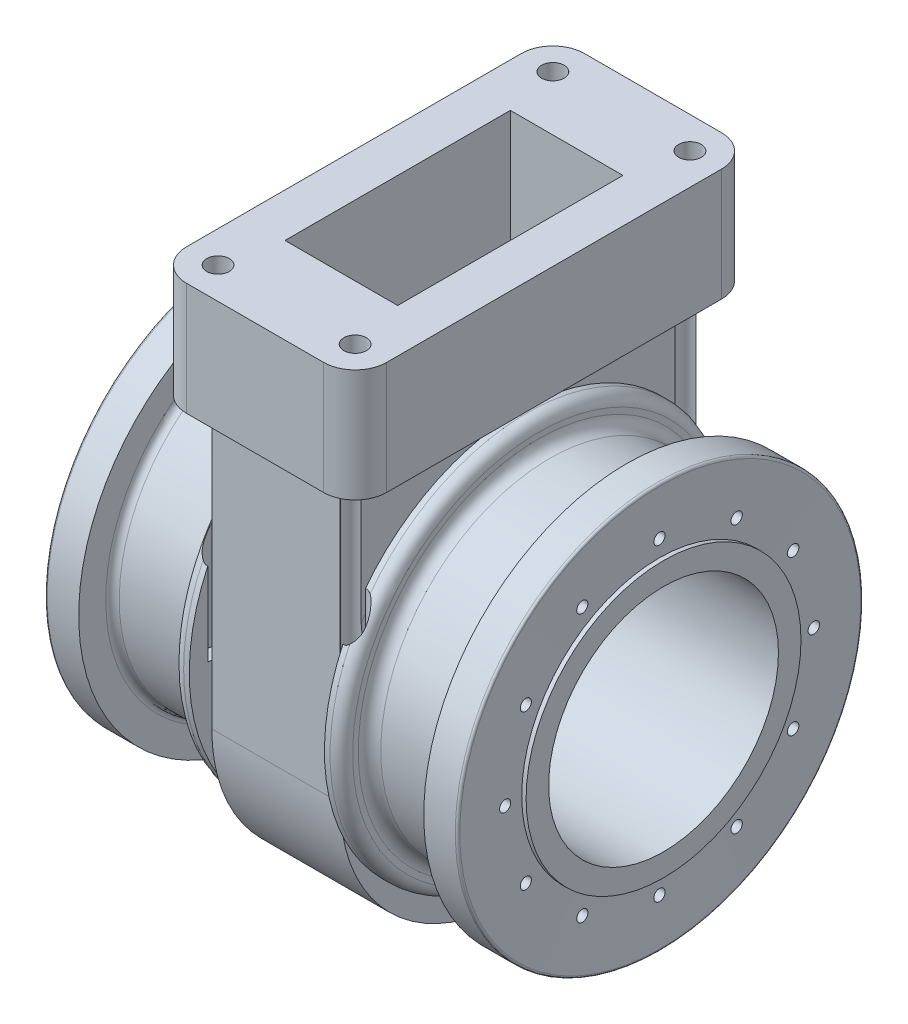
SolidWorks part; units mm, degrees
material "Gray Cast Iron"
ref_plane "Front Plane" through (0, 0, 0) normal (0, 0, 1) x (1, 0, 0)
ref_plane "Top Plane" through (0, 0, 0) normal (0, 1, 0) x (1, 0, 0)
ref_plane "Right Plane" through (0, 0, 0) normal (1, 0, 0) x (0, 0, -1)
sketch "Sketch1" plane through (0, 0, 0) normal (0, 0, 1) x (1, 0, 0)
  line L0 (-180, 0) -> (180, 0) construction
  line L1 (-180, 0) -> (180, 0)
  line L2 (-180, 0) -> (-183.1064, 177.9651)
  line L3 (-181.1067, 180) -> (-153.1419, 180)
  line L4 (-153.1419, 180) -> (-153.1419, 150)
  line L5 (153.1419, 180) -> (153.1419, 150)
  line L6 (181.1067, 180) -> (153.1419, 180)
  line L7 (180, 0) -> (183.1064, 177.9651)
  line L8 (-153.1419, 150) -> (153.1419, 150)
  arc A0 (-183.1064, 177.9651) -> (-181.1067, 180) centre (-181.1067, 178) cw
  arc A1 (183.1064, 177.9651) -> (181.1067, 180) centre (181.1067, 178) ccw
  point P6 (0, 0)
  point P14 (-183.1419, 180)
  point P17 (183.1419, 180)
  dimension "D5" = 2
  dimension "D8" = 2
  dimension "D1" = 30
  dimension "D2" = 30
  dimension "D3" = 91
  dimension "D4" = 180
  dimension "D6" = 30
  dimension "D7" = 30
  dimension "D9" = 360
  dimension "D10" = 0
revolve "Revolve4" add sketch "Sketch1" angle 360 about L0
ref_plane "Plane1" through (180, 0, 0) normal (1, 0, 0) x (0, 0, -1)
sketch "Sketch4" plane through (180, 0, 0) normal (1, 0, 0) x (0, 0, -1)
  circle A0 centre (0, 0) radius 122
extrude "Boss-Extrude1" add sketch "Sketch4" along normal blind 6
sketch "Sketch5" plane through (180, 0, 0) normal (1, 0, 0) x (0, 0, -1)
  circle A0 centre (0, 0) radius 102
extrude "Cut-Extrude2" cut sketch "Sketch5" against normal through all and the other way through all
ref_plane "Plane2" through (-180, 0, 0) normal (1, 0, 0) x (0, 0, -1)
sketch "Sketch7" plane through (-180, 0, 0) normal (1, 0, 0) x (0, 0, -1)
  circle A0 centre (0, 0) radius 122
extrude "Boss-Extrude2" add sketch "Sketch7" against normal blind 6
sketch "Sketch8" plane through (-186, 0, 0) normal (-1, 0, 0) x (0, 0, 1)
  circle A0 centre (0, 0) radius 102
extrude "Cut-Extrude5" cut sketch "Sketch8" along normal blind 6 and the other way through all
ref_plane "Plane3" through (0, 0, 0) normal (1, 0, 0) x (0, 0, -1)
sketch "Sketch9" plane through (0, 0, 0) normal (1, 0, 0) x (0, 0, -1)
  line L0 (0, 177.9651) -> (0, -177.9651) construction
  line L1 (-177.9651, 0) -> (177.9651, 0) construction
  line L2 (127.7612, 123.8897) -> (-123.8897, -127.7612) construction
  line L3 (-127.7612, 123.8897) -> (123.8897, -127.7612) construction
  circle A0 centre (0, 0) radius 137 construction
  circle A1 centre (0, 0) radius 177.9651 construction
  circle A3 centre (0, 137) radius 5
  dimension "D1" = 45
  dimension "D3" = 10
  dimension "D2" = 45
extrude "Cut-Extrude7" cut sketch "Sketch9" against normal through all and the other way through all
pattern_circular "CirPattern1" count 12 over 360 about axis through (-183.1067, 0, 0) along (1, 0, 0) of "Cut-Extrude7" reverse direction yes
fillet "Fillet1" radius 6 2 edges at (-153.1419, -150, 0) (153.1419, -150, 0)
sketch "Sketch10" plane through (0, 0, 0) normal (0, 1, 0) x (1, 0, 0)
  line L1 (-57, -158) -> (57, -158)
  line L2 (-57, -158) -> (-57, 158)
  line L3 (-57, 158) -> (57, 158)
  line L4 (57, -158) -> (57, 158)
  line L5 (0, 158) -> (0, -158) construction
  line L6 (-57, 0) -> (57, 0) construction
  point P0 (0, 0)
  dimension "D1" = 316
  dimension "D2" = 114
extrude "Boss-Extrude3" add sketch "Sketch10" along normal blind 200 and the other way blind 200
sketch "Sketch12" plane through (0, 200, 0) normal (0, 1, 0) x (1, 0, 0)
  line L1 (-60.8454, -176.609) -> (60.8454, -176.609)
  line L2 (-88.8454, -148.609) -> (-88.8454, 148.609)
  line L3 (-60.8454, 176.609) -> (60.8454, 176.609)
  line L4 (88.8454, -148.609) -> (88.8454, 148.609)
  line L5 (0, 176.609) -> (0, -176.609) construction
  line L6 (-88.8454, 0) -> (88.8454, 0) construction
  arc A0 (-60.8454, 176.609) -> (-88.8454, 148.609) centre (-60.8454, 148.609) ccw
  arc A1 (60.8454, 176.609) -> (88.8454, 148.609) centre (60.8454, 148.609) cw
  arc A2 (-88.8454, -148.609) -> (-60.8454, -176.609) centre (-60.8454, -148.609) ccw
  arc A3 (88.8454, -148.609) -> (60.8454, -176.609) centre (60.8454, -148.609) cw
  point P0 (0, 0)
  dimension "D1" = 28
extrude "Boss-Extrude4" add sketch "Sketch12" along normal blind 100
sketch "Sketch13" plane through (0, 300, 0) normal (0, 1, 0) x (1, 0, 0)
  line L1 (-50, -100) -> (50, -100)
  line L2 (-50, -100) -> (-50, 100)
  line L3 (-50, 100) -> (50, 100)
  line L4 (50, -100) -> (50, 100)
  line L5 (0, 100) -> (0, -100) construction
  line L6 (-50, 0) -> (50, 0) construction
  point P0 (0, 0)
  dimension "D1" = 200
  dimension "D2" = 100
fillet "Fillet3" radius 150 1 edges at (0, -200, 158) type face fillet first side face at (0, 0, 158) second side face at (0, -200, 0)
fillet "Fillet4" radius 150 1 edges at (0, -200, -158) type face fillet first side face at (0, -200, -75) second side face at (0, 0, -158)
extrude "Cut-Extrude12" cut sketch "Sketch13" against normal blind 300
sketch "Sketch14" plane through (0, 0, 0) normal (0, 1, 0) x (1, 0, 0)
  circle A0 centre (-51.781, 164.2561) radius 8.6568
ref_plane "Plane4" through (0, -180, 0) normal (0, 1, 0) x (1, 0, 0)
sketch "Sketch18" plane through (57, 0, 0) normal (1, 0, 0) x (0, 0, -1)
  circle A0 centre (0, 0) radius 102
extrude "Cut-Extrude14" cut sketch "Sketch18" against normal through all and the other way through all
fillet "Fillet10" radius 10 1 edges at (57, 0, -150)
fillet "Fillet11" radius 10 1 edges at (-57, 0, 150)
ref_plane "Plane5" through (60, 0, 0) normal (1, 0, 0) x (0, 0, -1)
sketch "Sketch19" plane through (60, 0, 0) normal (1, 0, 0) x (0, 0, -1)
  circle A0 centre (0, 0) radius 175
  dimension "D1" = 350
extrude "Boss-Extrude10" add sketch "Sketch19" along normal blind 15
mirror "Mirror4" about plane through (0, 0, 0) normal (1, 0, 0) of "Boss-Extrude10"
fillet "Fillet14" radius 10 4 edges at (75, 0, -150) (75, 0, -175) (-75, 0, 150) (-75, 0, -175)
sketch "Sketch20" plane through (0, 0, 0) normal (1, 0, 0) x (0, 0, -1)
  circle A0 centre (0, 0) radius 102
extrude "Cut-Extrude15" cut sketch "Sketch20" against normal through all and the other way through all
sketch "Sketch22" plane through (0, 0, 0) normal (0, 1, 0) x (1, 0, 0)
  circle A0 centre (60.8454, 148.609) radius 10
  circle A1 centre (60.8454, -148.609) radius 10
  circle A2 centre (-60.8454, -148.609) radius 10
  circle A3 centre (-60.8454, 148.609) radius 10
  dimension "D1" = 20
extrude "Cut-Extrude16" cut sketch "Sketch22" along normal up to next
equation "\"l\"= 360"
